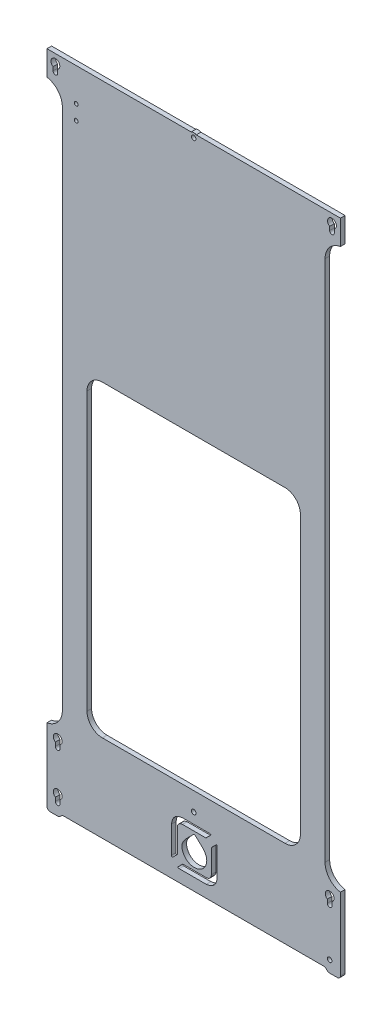
SolidWorks part; units mm, degrees
material "6061-T6 Black anodised"
ref_plane "Front Plane" through (0, 0, 0) normal (0, 0, 1) x (1, 0, 0)
ref_plane "Top Plane" through (0, 0, 0) normal (0, 1, 0) x (1, 0, 0)
ref_plane "Right Plane" through (0, 0, 0) normal (1, 0, 0) x (0, 0, -1)
sketch "Sketch1" plane through (0, 0, 0) normal (0, 0, 1) x (1, 0, 0)
  line L0 (88.27, 0) -> (-88.27, 0) construction
  line L1 (95.27, 389.5) -> (-95.27, 389.5)
  line L2 (95.27, 389.5) -> (95.27, -36.5)
  line L3 (85.27, -36.5) -> (-85.27, -36.5)
  line L4 (-95.27, 389.5) -> (-95.27, -36.5)
  line L5 (95.27, 389.5) -> (-95.27, -36.5) construction
  line L6 (95.27, -36.5) -> (-95.27, 389.5) construction
  line L7 (-89.77, -31) -> (-89.77, -28.5767)
  line L8 (-89.77, 379) -> (89.77, 379) construction
  line L9 (0, 379) -> (0, 0) construction
  line L10 (-91.27, 379) -> (-91.27, 381.4233)
  line L11 (-88.27, 379) -> (-88.27, 381.4233)
  line L12 (-89.77, 0) -> (-89.77, 2.4233)
  line L13 (-86.77, 0) -> (-86.77, 2.4233)
  line L14 (-86.77, -31) -> (-86.77, -28.5767)
  line L15 (86.77, -31) -> (86.77, -28.5767) construction
  line L16 (89.77, -31) -> (89.77, -28.5767) construction
  line L17 (86.77, 0) -> (86.77, 2.4233)
  line L18 (89.77, 0) -> (89.77, 2.4233)
  line L19 (88.27, 379) -> (88.27, 381.4233)
  line L20 (91.27, 379) -> (91.27, 381.4233)
  line L21 (-95.27, -36.5) -> (-95.27, -38.5)
  line L22 (-95.27, -38.5) -> (-87.27, -38.5)
  line L23 (-87.27, -38.5) -> (-85.27, -36.5)
  line L24 (95.27, -36.5) -> (95.27, -38.5)
  line L25 (95.27, -38.5) -> (87.27, -38.5)
  line L26 (87.27, -38.5) -> (85.27, -36.5)
  arc A0 (-89.77, 0) -> (-86.77, 0) centre (-88.27, 0) ccw
  arc A1 (86.77, 0) -> (89.77, 0) centre (88.27, 0) ccw
  arc A2 (-89.77, -31) -> (-86.77, -31) centre (-88.27, -31) ccw
  arc A3 (86.77, -31) -> (89.77, -31) centre (88.27, -31) ccw construction
  arc A4 (-91.27, 379) -> (-88.27, 379) centre (-89.77, 379) ccw
  arc A5 (88.27, 379) -> (91.27, 379) centre (89.77, 379) ccw
  arc A6 (-88.27, 381.4233) -> (-91.27, 381.4233) centre (-89.77, 383.8466) ccw
  circle A7 centre (-89.77, 379) radius 2.85 construction
  arc A8 (-86.77, 2.4233) -> (-89.77, 2.4233) centre (-88.27, 4.8466) ccw
  circle A9 centre (-88.27, 0) radius 2.85 construction
  arc A10 (-86.77, -28.5767) -> (-89.77, -28.5767) centre (-88.27, -26.1534) ccw
  circle A11 centre (-88.27, -31) radius 2.85 construction
  arc A12 (89.77, -28.5767) -> (86.77, -28.5767) centre (88.27, -26.1534) ccw construction
  circle A13 centre (88.27, -31) radius 2.85 construction
  arc A14 (89.77, 2.4233) -> (86.77, 2.4233) centre (88.27, 4.8466) ccw
  circle A15 centre (88.27, 0) radius 2.85 construction
  arc A16 (91.27, 381.4233) -> (88.27, 381.4233) centre (89.77, 383.8466) ccw
  circle A17 centre (89.77, 379) radius 2.85 construction
  circle A18 centre (88.27, -31) radius 1.5
  point P0 (0, 176.5)
  dimension "D4" = 3
  dimension "D7" = 5.5
  dimension "D9" = 5.7
  dimension "D1" = 190.54
  dimension "D2" = 426
  dimension "D3" = 7
  dimension "D5" = 31
  dimension "D6" = 5.5
  dimension "D8" = 10.5
  dimension "D10" = 45
  dimension "D11" = 8
  dimension "D12" = 2
extrude "Boss-Extrude1" add sketch "Sketch1" along normal blind 3
sketch "Sketch2" plane through (0, 0, 3) normal (0, 0, 1) x (1, 0, 0)
  line L0 (-95.27, 389.5) -> (-95.27, -38.5) construction
  line L1 (-95.27, 10.5) -> (-85.27, 10.5)
  line L2 (-95.27, 10.5) -> (-95.27, 373.5)
  line L3 (-95.27, 373.5) -> (-85.27, 373.5)
  line L4 (-85.27, 10.5) -> (-85.27, 373.5)
  line L5 (95.27, -38.5) -> (95.27, 389.5) construction
  line L6 (95.27, 10.5) -> (85.27, 10.5)
  line L7 (95.27, 10.5) -> (95.27, 373.5)
  line L8 (95.27, 373.5) -> (85.27, 373.5)
  line L9 (85.27, 10.5) -> (85.27, 373.5)
  line L10 (95.27, 389.5) -> (-95.27, 389.5) construction
  line L11 (-85.27, -36.5) -> (85.27, -36.5) construction
  dimension "D1" = 16
  dimension "D2" = 47
  dimension "D3" = 10
extrude "Cut-Extrude1" cut sketch "Sketch2" against normal through all
fillet "Fillet1" radius 12 4 edges at (85.27, 10.5, 1.5) (-85.27, 10.5, 1.5) (85.27, 373.5, 1.5) (-85.27, 373.5, 1.5)
sketch "Sketch3" plane through (0, 0, 3) normal (0, 0, 1) x (1, 0, 0)
  line L0 (-85.27, -36.5) -> (85.27, -36.5) construction
  line L1 (95.27, 389.5) -> (-95.27, 389.5) construction
  circle A0 centre (0, 8) radius 1.5
  circle A1 centre (-88.27, 0) radius 1.5 construction
  circle A2 centre (0, 387) radius 1.5
  dimension "D2" = 2.5
  dimension "D1" = 44.5
extrude "Cut-Extrude2" cut sketch "Sketch3" against normal through all
sketch "Sketch4" plane through (0, 0, 3) normal (0, 0, 1) x (1, 0, 0)
  line L0 (-85.27, 22.3322) -> (-85.27, 361.6678) construction
  line L1 (-69.27, 220) -> (69.27, 220)
  line L2 (-69.27, 220) -> (-69.27, 20)
  line L3 (-69.27, 20) -> (69.27, 20)
  line L4 (69.27, 220) -> (69.27, 20)
  line L5 (-69.27, 220) -> (69.27, 20) construction
  line L6 (-69.27, 20) -> (69.27, 220) construction
  circle A0 centre (0, 8) radius 1.5 construction
  point P0 (0, 120)
  dimension "D1" = 16
  dimension "D2" = 12
  dimension "D3" = 200
extrude "Cut-Extrude3" cut sketch "Sketch4" against normal through all
fillet "Fillet2" radius 10 4 edges at (69.27, 220, 1.5) (-69.27, 220, 1.5) (69.27, 20, 1.5) (-69.27, 20, 1.5)
sketch "Sketch7" plane through (0, 0, 3) normal (0, 0, 1) x (1, 0, 0)
  line L0 (0, -4.6257) -> (-4.8534, -9.4789)
  line L1 (6.0015, -9.4789) -> (0.8516, -4.6257)
  line L2 (-7.2622, -2.659) -> (7.8165, -2.659)
  line L3 (8.077, -2.549) -> (11.0039, 0.3781)
  line L4 (10.2253, 1.0822) -> (-7.2622, 1.0822)
  line L5 (-14.4113, -6.0673) -> (-14.4098, -23.5545)
  line L6 (-13.7057, -24.3315) -> (-10.7801, -21.4046)
  line L7 (-10.6686, -21.1457) -> (-10.67, -6.0673)
  line L8 (8.1139, -24.8541) -> (-6.9645, -24.8541)
  line L9 (-7.2249, -24.9656) -> (-10.1519, -27.8925)
  line L10 (-9.3733, -28.5967) -> (8.1139, -28.5967)
  line L11 (15.2633, -21.4459) -> (15.2619, -3.9601)
  line L12 (14.5577, -3.1829) -> (11.6308, -6.1099)
  line L13 (11.5207, -6.3688) -> (11.5218, -21.4459)
  spline S0 degree 3 poles (0.4439, -4.4409) (0.3912, -4.446) (0.2828, -4.4565) (0.1286, -4.5203) (0.0426, -4.5908) (0, -4.6257) knots 0 0 0 0 0.322338 0.663828 1 1 1 1
  spline S1 degree 3 poles (-4.8534, -9.4789) (-4.8579, -9.4831) (-4.8667, -9.4912) (-4.8791, -9.5037) (-5.3375, -10.01) (-6.231, -11.0554) (-7.3312, -12.8598) (-7.8887, -15.6825) (-6.8483, -19.2199) (-3.8783, -22.1689) (0.2577, -23.4427) (4.5569, -22.3845) (7.7118, -19.2149) (8.7217, -15.6934) (8.2109, -12.8985) (7.2971, -11.0248) (6.4234, -9.9823) (6.0015, -9.4789) knots 0 0 0 0 0.000489 0.000958 0.001407 0.055151 0.111018 0.168413 0.280621 0.389777 0.490762 0.614387 0.723194 0.83533 0.891393 0.947551 1 1 1 1
  spline S2 degree 3 poles (0.8516, -4.6257) (0.8125, -4.5919) (0.7352, -4.5249) (0.5954, -4.4557) (0.4944, -4.4458) (0.4439, -4.4409) knots 0 0 0 0 0.338885 0.669777 1 1 1 1
  spline S3 degree 3 poles (7.8165, -2.659) (7.8386, -2.6573) (7.882, -2.6541) (7.9472, -2.6464) (7.9964, -2.6204) (8.0324, -2.5949) (8.0557, -2.5715) (8.07, -2.5564) (8.077, -2.549) knots 0 0 0 0 0.227493 0.445972 0.663373 0.787115 0.896006 1 1 1 1
  spline S4 degree 3 poles (11.0039, 0.3781) (11.0329, 0.4173) (11.0909, 0.496) (11.1149, 0.6442) (11.0877, 0.7801) (11.0204, 0.8896) (10.9299, 0.9685) (10.7969, 1.0179) (10.6368, 1.0502) (10.4517, 1.0835) (10.3213, 1.081) (10.25, 1.0825) (10.2377, 1.0831) (10.2294, 1.0825) (10.2253, 1.0822) knots 0 0 0 0 0.104345 0.208931 0.313565 0.397995 0.482811 0.567894 0.701187 0.836715 0.973247 0.982163 0.991064 1 1 1 1
  spline S5 degree 3 poles (-7.2622, 1.0822) (-8.5111, 0.8827) (-10.9772, 0.4887) (-13.8177, -2.3518) (-14.2117, -4.8181) (-14.4113, -6.0673) knots 0 0 0 0 0.336154 0.663772 1 1 1 1
  spline S6 degree 3 poles (-14.4098, -23.5545) (-14.4101, -23.5584) (-14.4107, -23.5663) (-14.4101, -23.5782) (-14.4085, -23.6494) (-14.4116, -23.78) (-14.3778, -23.9655) (-14.348, -24.1263) (-14.2965, -24.2584) (-14.2178, -24.3487) (-14.1086, -24.4167) (-13.9724, -24.4439) (-13.8239, -24.4196) (-13.7451, -24.3609) (-13.7057, -24.3315) knots 0 0 0 0 0.008622 0.017031 0.025643 0.162638 0.298245 0.431901 0.516392 0.601007 0.685957 0.790142 0.895037 1 1 1 1
  spline S7 degree 3 poles (-10.7801, -21.4046) (-10.7711, -21.3953) (-10.7536, -21.3772) (-10.7264, -21.3501) (-10.6977, -21.3146) (-10.6778, -21.2655) (-10.6682, -21.2062) (-10.6685, -21.1664) (-10.6686, -21.1457) knots 0 0 0 0 0.131285 0.25763 0.390972 0.594165 0.788898 1 1 1 1
  spline S8 degree 3 poles (-10.67, -6.0673) (-10.5818, -5.4634) (-10.4093, -4.283) (-9.0474, -2.92) (-7.8666, -2.7474) (-7.2622, -2.659) knots 0 0 0 0 0.33841 0.661392 1 1 1 1
  spline S9 degree 3 poles (-6.9645, -24.8541) (-6.9836, -24.8548) (-7.0187, -24.8562) (-7.0727, -24.8646) (-7.117, -24.885) (-7.157, -24.9087) (-7.1915, -24.9347) (-7.2134, -24.955) (-7.2249, -24.9656) knots 0 0 0 0 0.196746 0.361608 0.557262 0.692766 0.839563 1 1 1 1
  spline S10 degree 3 poles (-10.1519, -27.8925) (-10.1809, -27.9318) (-10.2389, -28.0105) (-10.2629, -28.1587) (-10.2357, -28.2947) (-10.1681, -28.4041) (-10.0777, -28.4828) (-9.9452, -28.5327) (-9.7851, -28.5653) (-9.6, -28.5955) (-9.4695, -28.601) (-9.3981, -28.5958) (-9.3857, -28.5965) (-9.3774, -28.5966) (-9.3733, -28.5967) knots 0 0 0 0 0.104385 0.20895 0.313569 0.398093 0.483012 0.567612 0.700915 0.836485 0.973043 0.982112 0.991066 1 1 1 1
  spline S11 degree 3 poles (8.1139, -28.5967) (9.3629, -28.3971) (11.8293, -28.0028) (14.6704, -25.162) (15.064, -22.6952) (15.2633, -21.4459) knots 0 0 0 0 0.336157 0.663806 1 1 1 1
  spline S12 degree 3 poles (15.2619, -3.9601) (15.2622, -3.956) (15.2628, -3.9477) (15.2621, -3.9352) (15.2606, -3.8638) (15.2632, -3.7334) (15.2298, -3.5483) (15.198, -3.3882) (15.148, -3.2557) (15.0694, -3.1653) (14.9599, -3.0977) (14.8239, -3.0705) (14.6754, -3.0949) (14.597, -3.1536) (14.5577, -3.1829) knots 0 0 0 0 0.008953 0.017947 0.027021 0.163491 0.298949 0.432165 0.516776 0.601601 0.686035 0.790672 0.895263 1 1 1 1
  spline S13 degree 3 poles (11.6308, -6.1099) (11.6212, -6.1191) (11.6023, -6.1372) (11.5737, -6.165) (11.5433, -6.1982) (11.5265, -6.2477) (11.5219, -6.3062) (11.5211, -6.3471) (11.5207, -6.3688) knots 0 0 0 0 0.134582 0.264928 0.404991 0.586048 0.77989 1 1 1 1
  spline S14 degree 3 poles (11.5218, -21.4459) (11.4339, -22.05) (11.262, -23.2307) (9.8992, -24.5934) (8.7183, -24.7658) (8.1139, -24.8541) knots 0 0 0 0 0.338406 0.661372 1 1 1 1
extrude "Cut-Extrude6" cut sketch "Sketch7" against normal through all
sketch "Sketch8" plane through (0, 0, 3) normal (0, 0, 1) x (1, 0, 0)
  line L0 (95.27, 389.5) -> (-95.27, 389.5) construction
  line L1 (-1.6583, 389.5) -> (1.6583, 389.5)
  arc A0 (1.6583, 389.5) -> (-1.6583, 389.5) centre (0, 387) ccw
  dimension "D1" = 3
extrude "Boss-Extrude2" add sketch "Sketch8" against normal up to surface (3 mm away) up to face at (5.0456, -18.6663, 0)
sketch "Sketch9" plane through (0, 0, 3) normal (0, 0, 1) x (1, 0, 0)
  line L0 (-1.6583, 389.5) -> (-95.27, 389.5) construction
  line L1 (-85.27, 22.3322) -> (-85.27, 361.6678) construction
  circle A0 centre (-76.27, 368) radius 1.25
  circle A1 centre (-76.27, 358.5) radius 1.25
  dimension "D1" = 2.5
  dimension "D3" = 21.5
  dimension "D4" = 9
  dimension "D2" = 9.5
extrude "Cut-Extrude7" cut sketch "Sketch9" against normal through all
fillet "Fillet3" radius 2 6 edges at (85.27, -36.5, 1.5) (87.27, -38.5, 1.5) (95.27, -38.5, 1.5) (-85.27, -36.5, 1.5) (-87.27, -38.5, 1.5) (-95.27, -38.5, 1.5)
